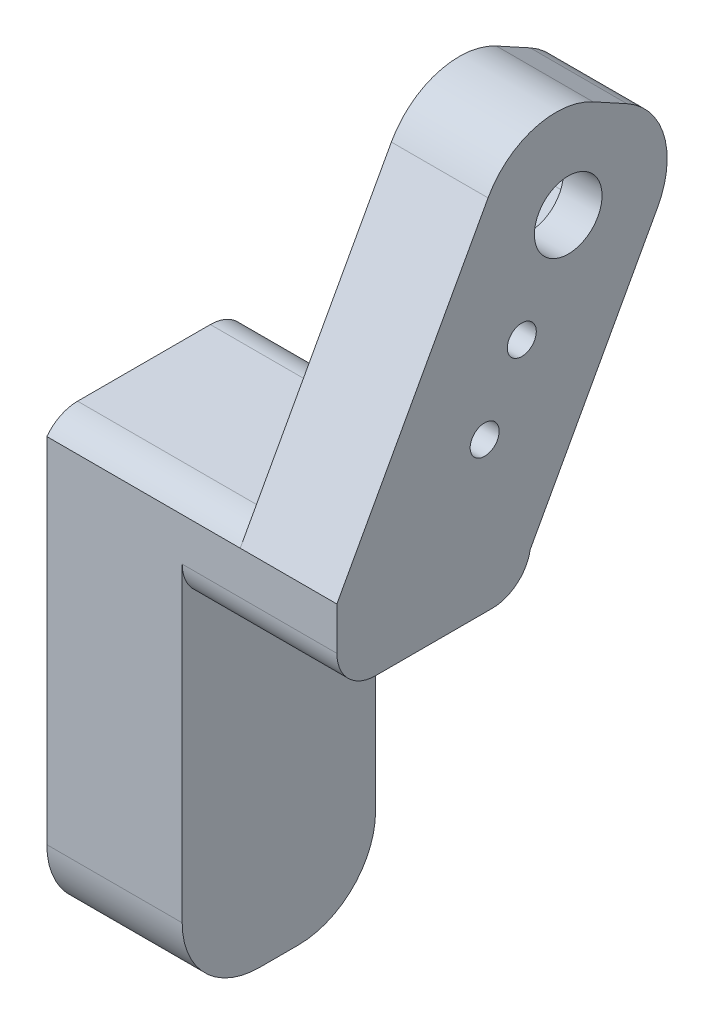
SolidWorks part; units mm, degrees
ref_plane "Front" through (0, 0, 0) normal (0, 0, 1) x (1, 0, 0)
ref_plane "Top" through (0, 0, 0) normal (0, 1, 0) x (1, 0, 0)
ref_plane "Right" through (0, 0, 0) normal (1, 0, 0) x (0, 0, -1)
sketch "Sketch3" plane through (0, 0, 0) normal (1, 0, 0) x (0, 0, -1)
  line L0 (0, 0) -> (-9.1244, -16.6657)
  line L3 (-9.1244, -16.6657) -> (-9.1244, -37.6657)
  dimension "D1" = 19
  dimension "D2" = 21
extrude "Extrude-Thin1" add sketch "Sketch3" along normal blind 15 thin thin type mid plane wall 10
sketch "Sketch4" plane through (0, 0, 14.1244) normal (0, 0, 1) x (1, 0, 0)
  line L0 (15, 2.4012) -> (10, 2.4012)
  line L1 (15, 2.4012) -> (0, 2.4012) construction
  line L2 (10, 2.4012) -> (10, -14.5988)
  line L3 (10, -14.5988) -> (0, -14.5988)
  line L4 (0, -14.5988) -> (0, -37.6657)
  line L5 (15, -37.6657) -> (0, -37.6657) construction
  line L6 (0, -37.6657) -> (7, -37.6657)
  line L7 (7, -37.6657) -> (7, -19.5988)
  line L8 (7, -19.5988) -> (15, -19.5988)
  line L9 (15, -15.3865) -> (15, -37.6657) construction
  line L10 (15, -19.5988) -> (15, 2.4012)
  dimension "D1" = 5
  dimension "D2" = 7
  dimension "D3" = 10
  dimension "D4" = 5
  dimension "D5" = 17
extrude "Cut-Extrude1" cut sketch "Sketch4" against normal through all flip side to cut
sketch "Sketch6" plane through (10, 0, 0) normal (-1, 0, 0) x (0, 0, 1)
  line L0 (0, 0) -> (13.9959, -25.5635) construction
  line L1 (13.6931, -14.5988) -> (4.3857, 2.4012) construction
  line L2 (-0.922, -6.082) -> (5.1503, -14.8513)
  line L3 (5.1503, -14.8513) -> (9.7369, -12.3401)
  line L4 (9.7369, -12.3401) -> (5.6205, -2.5)
  line L5 (-4.3857, -2.4012) -> (4.3857, 2.4012) construction
  arc A0 (5.6205, -2.5) -> (-0.922, -6.082) centre (2.161, -3.9471) ccw
  dimension "D1" = 7.5
  dimension "D2" = 11
  dimension "D3" = 4.5
  dimension "D4" = 12
extrude "Cut-Extrude2" cut sketch "Sketch6" against normal blind 3
sketch "Sketch7" plane through (13, 0, 0) normal (-1, 0, 0) x (0, 0, 1)
  line L0 (2.161, -3.9471) -> (7.8493, -14.3368) construction
  line L1 (13.6931, -14.5988) -> (4.3857, 2.4012) construction
  circle A0 centre (2.161, -3.9471) radius 1.75
  circle A1 centre (4.5622, -8.3328) radius 0.75
  circle A2 centre (6.4831, -11.8414) radius 0.75
  dimension "D1" = 3.5
  dimension "D2" = 1.5
  dimension "D3" = 4
  dimension "D4" = 5
extrude "Cut-Extrude3" cut sketch "Sketch7" against normal through all
fillet "Fillet1" radius 4 4 edges at (3.5, -37.6657, 14.1244) (3.5, -37.6657, 4.1244) (12.5, -2.4012, -4.3857) (12.5, 2.4012, 4.3857)
fillet "Fillet2" radius 2 2 edges at (11, -19.5988, 14.1244) (11, -19.5988, 4.1244)
fillet "Fillet3" radius 2 2 edges at (5, -14.5988, 2.2925) (5, -14.5988, 13.6931)
